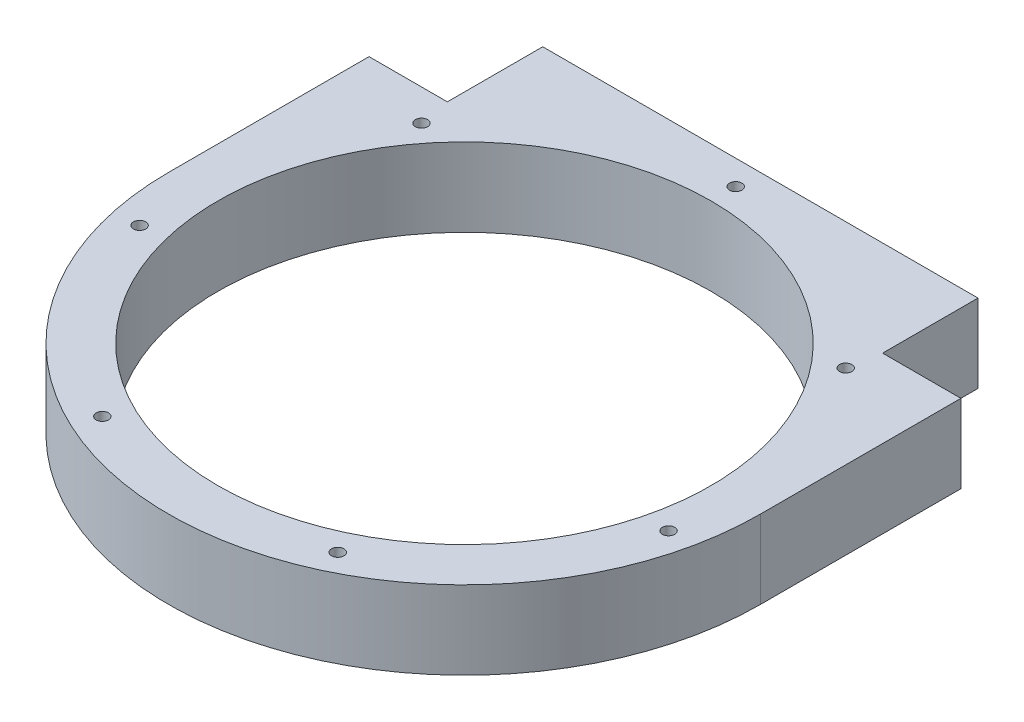
SolidWorks part; units mm, degrees
ref_plane "Front Plane" through (0, 0, 0) normal (0, 0, 1) x (1, 0, 0)
ref_plane "Top Plane" through (0, 0, 0) normal (0, 1, 0) x (1, 0, 0)
ref_plane "Right Plane" through (0, 0, 0) normal (1, 0, 0) x (0, 0, -1)
ref_axis "X Axis" through (-88.99, 0, 0) along (1, 0, 0)
ref_axis "Y Axiz" through (0, 0, 55) along (0, 0, -1)
ref_axis "Z Axis" through (0, 55, 0) along (0, -1, 0)
sketch "Sketch1" plane through (0, 0, 0) normal (0, 1, 0) x (1, 0, 0)
  line L1 (34.4006, 27.4336) -> (31.2733, 24.9396) construction
  line L2 (0, 48) -> (-35.3, 48)
  line L3 (-35.3, 48) -> (-35.3, 32.5255)
  line L4 (-35.3, 32.5255) -> (-48, 32.5255)
  line L5 (-48, 32.5255) -> (-48, 0)
  line L6 (48, 0) -> (-48, 0)
  line L8 (48, 0) -> (48, 32.5255)
  line L9 (48, 32.5255) -> (35.3, 32.5255)
  line L10 (35.3, 32.5255) -> (35.3, 48)
  line L11 (35.3, 48) -> (0, 48)
  circle A0 centre (0, 0) radius 40
  circle A1 centre (0, 0) radius 48
  circle A2 centre (0, 0) radius 44 construction
  circle A3 centre (0, 44) radius 1
  circle A4 centre (34.4006, 27.4336) radius 1
  circle A5 centre (42.8968, -9.7909) radius 1
  circle A6 centre (19.0909, -39.6426) radius 1
  circle A7 centre (-19.0909, -39.6426) radius 1
  circle A8 centre (-42.8968, -9.7909) radius 1
  circle A9 centre (-34.4006, 27.4336) radius 1
  point P24 (0, 0)
  dimension "D1" = 80
  dimension "D2" = 96
  dimension "D3" = 88
  dimension "D4" = 2
  dimension "D6" = 12.7
  dimension "D5" = 7
extrude "Boss-Extrude1" add sketch "Sketch1" along normal blind 12.7 contours A1 L10 L11 | A1 L8 L9 | A1 L2 L3 | A1 L4 L5 | L6 A1 A0 A9 A4 A3 | L6 A1 A0 A8 A7 A6 A5 region at (-26.7848, 0, -43.5217) region at (26.7848, 0, -43.5217) region at (18.8405, 0, -42.9785) region at (44.2953, 0, -24.625) region at (-44.2953, 0, -24.625) region at (0, 0, 46.9267)
